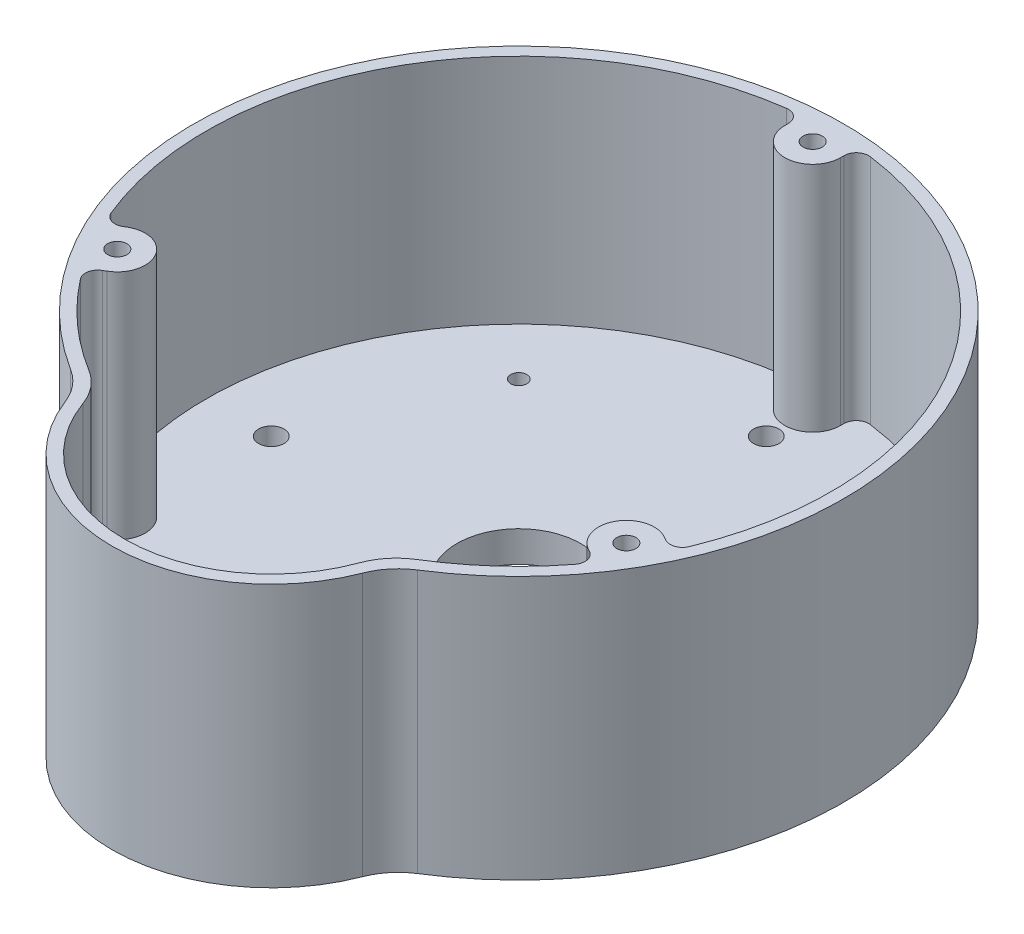
SolidWorks part; units mm, degrees
ref_plane "Plan de face" through (0, 0, 0) normal (0, 0, 1) x (1, 0, 0)
ref_plane "Plan de dessus" through (0, 0, 0) normal (0, 1, 0) x (1, 0, 0)
ref_plane "Plan de droite" through (0, 0, 0) normal (1, 0, 0) x (0, 0, -1)
sketch "Esquisse1" plane through (0, 0, 0) normal (0, 1, 0) x (1, 0, 0)
  line L0 (-51.4386, 28) -> (54.7147, 28) construction
  line L1 (-93.9383, 0) -> (92.9837, 0) construction
  line L2 (0, 84.3142) -> (0, -27.4159) construction
  line L3 (-79.8999, -42) -> (100.4836, -42) construction
  circle A0 centre (0, 0) radius 52.5
  circle A1 centre (0, 40) radius 2.05
  circle A2 centre (40, 0) radius 2.05
  circle A3 centre (0, -40) radius 2.05
  circle A4 centre (-40, 0) radius 2.05
  circle A5 centre (28, 28) radius 1.3
  circle A6 centre (20, -42) radius 1.3
  circle A7 centre (-20, -42) radius 1.3
  circle A8 centre (-28, 28) radius 1.3
  circle A9 centre (0, 0) radius 10
  point P14 (0, 0)
  dimension "D1" = 105
  dimension "D2" = 4.1
  dimension "D7" = 56
  dimension "D9" = 20
  dimension "D10" = 2.6
  dimension "D4" = 40
  dimension "D5" = 28
  dimension "D6" = 42
  dimension "D8" = 40
  dimension "D3" = 4
extrude "Boss.-Extru.2" add sketch "Esquisse1" along normal blind 5
sketch "Esquisse2" plane through (0, 5, 0) normal (0, 1, 0) x (1, 0, 0)
  line L0 (0, 90.2757) -> (0, -93.0238) construction
  line L1 (-4.5, 47.5) -> (-4.5, 50.2991) construction
  line L2 (4.5, 47.5) -> (4.5, 50.2991) construction
  line L3 (0, 0) -> (-88.0909, 50.8593) construction
  line L4 (0, 0) -> (91.089, 52.5902) construction
  line L5 (-4.5, 47.5) -> (-4.5, 48.0625)
  line L6 (4.5, 48.0625) -> (4.5, 47.5)
  line L7 (43.3862, -19.8529) -> (43.8733, -20.1341)
  line L8 (39.3733, -27.9283) -> (38.8862, -27.6471)
  line L9 (-38.8862, -27.6471) -> (-39.3733, -27.9283)
  line L10 (-43.8733, -20.1341) -> (-43.3862, -19.8529)
  circle A0 centre (0, 0) radius 50.5 construction
  circle A1 centre (0, 0) radius 52.5
  circle A2 centre (0, 0) radius 52.5
  circle A3 centre (0, 47.5) radius 4.5
  circle A4 centre (41.1362, -23.75) radius 4.5
  circle A5 centre (-41.1362, -23.75) radius 4.5
  arc A6 (-6.768, 50.0444) -> (-43.7343, 25.25) centre (0, 0) ccw
  arc A7 (6.768, 50.0444) -> (43.7343, 25.25) centre (0, 0) cw
  arc A8 (4.5, 48.0625) -> (6.768, 50.0444) centre (6.5, 48.0625) cw
  arc A9 (-6.768, 50.0444) -> (-4.5, 48.0625) centre (-6.5, 48.0625) cw
  arc A10 (46.7238, -19.1609) -> (43.7343, 25.25) centre (0, 0) ccw
  arc A11 (39.9557, -30.8835) -> (0, -50.5) centre (0, 0) cw
  arc A12 (39.3733, -27.9283) -> (39.9557, -30.8835) centre (38.3733, -29.6604) cw
  arc A13 (46.7238, -19.1609) -> (43.8733, -20.1341) centre (44.8733, -18.4021) cw
  arc A14 (-39.9557, -30.8835) -> (0, -50.5) centre (0, 0) ccw
  arc A15 (-46.7238, -19.1609) -> (-43.7343, 25.25) centre (0, 0) cw
  arc A16 (-43.8733, -20.1341) -> (-46.7238, -19.1609) centre (-44.8733, -18.4021) cw
  arc A17 (-39.9557, -30.8835) -> (-39.3733, -27.9283) centre (-38.3733, -29.6604) cw
  point P28 (0, 0)
  point P51 (0, 0)
  circle M7 centre (0, 0) radius 52.5
  dimension "D2" = 2
  dimension "D3" = 9
  dimension "D4" = 47.5
  dimension "D6" = 60
  dimension "D8" = 2
  dimension "D7" = 60
  dimension "D1" = 0
  dimension "D5" = 3
  dimension "D9" = 3
extrude "Boss.-Extru.3" add sketch "Esquisse2" along normal blind 37.5 contours A5 | A3 | A4 | A14 A17 L9 A5 L10 A16 A15 A6 A9 L5 A3 L6 A8 A7 A10 A13 L7 A4 L8 A12 A11 M7 region at (0, 5, -47.5) region at (-41.1362, 5, 23.75) region at (41.1362, 5, 23.75) region at (-51.0151, 5, 0)
sketch "Esquisse3" plane through (0, 42.5, 0) normal (0, 1, 0) x (1, 0, 0)
  circle A0 centre (0, 47.5) radius 3.35
  circle A3 centre (41.1362, -23.75) radius 3.35
  circle A4 centre (-41.1362, -23.75) radius 3.35
  circle A9 centre (0, 0) radius 52.5
  circle A10 centre (0, 0) radius 52.5
  point P13 (0, 0)
  dimension "D2" = 3
  dimension "D3" = 6.7
  dimension "D1" = 0
extrude "Enlèv. mat.-Extru.1" cut sketch "Esquisse3" against normal through all from offset 4 contours A0 | A4 | A3 offset against normal yes
sketch "Esquisse5" plane through (0, 42.5, 0) normal (0, 1, 0) x (1, 0, 0)
  arc A0 (-4.5, 47.5) -> (4.5, 47.5) centre (0, 47.5) ccw construction
  arc A1 (-4.5, 47.5) -> (4.5, 47.5) centre (0, 47.5) ccw
  circle A2 centre (0, 47.5) radius 1.55
  circle A3 centre (41.1362, -23.75) radius 1.55
  circle A4 centre (-41.1362, -23.75) radius 1.55
  point P11 (0, 0)
  dimension "D1" = 3.1
  dimension "D2" = 3
extrude "Enlèv. mat.-Extru.3" cut sketch "Esquisse5" against normal through all contours A4 | A3 | A2 region at (0, 42.5, -47.5) region at (41.1362, 42.5, 23.75) region at (-41.1362, 42.5, 23.75)
sketch "Esquisse6" plane through (0, 0, 0) normal (0, -1, 0) x (1, 0, 0)
  circle A0 centre (-20, 42) radius 3.75
  circle A1 centre (0, 0) radius 52.5
  circle A3 centre (20, 42) radius 3.75
  circle A4 centre (-28, -28) radius 3.75
  circle A5 centre (28, -28) radius 3.75
  circle A15 centre (0, 0) radius 52.5
  dimension "D2" = 7.5
  dimension "D1" = 0
extrude "Enlèv. mat.-Extru.4" cut sketch "Esquisse6" against normal blind 3 contours A0 | A3 | A5 | A4
sketch "Esquisse7" plane through (0, 0, 0) normal (0, 0, 1) x (1, 0, 0)
  line L0 (0, 56.3049) -> (0, -34.4214) construction
  line L1 (-52.5, 0) -> (52.5, 0) construction
  line L2 (-52.5, 0) -> (52.5, 0)
  line L3 (52.5, 42.5) -> (-52.5, 42.5) construction
  line L4 (52.5, 42.5) -> (-52.5, 42.5)
  line L5 (-25, 42.5) -> (-25, 5)
  line L6 (-25, 5) -> (25, 5)
  line L7 (25, 5) -> (25, 42.5)
  line L8 (-25, 42.5) -> (25, 42.5)
  dimension "D1" = 5
  dimension "D2" = 25
extrude "Enlèv. mat.-Extru.5" cut sketch "Esquisse7" along normal through all contours L0 L8 L5 L6 | L4 L0 L6 L7 region at (12.5, 23.75, 0) region at (-12.5, 23.75, 0)
sketch "Esquisse8" plane through (0, 0, 0) normal (0, 1, 0) x (1, 0, 0)
  line L0 (0, 4.2422) -> (0, -58.8142) construction
  line L6 (25, -46.1655) -> (25, -43.8777)
  line L7 (25, -46.1655) -> (25, -43.8777)
  line L8 (-38.8862, -27.6471) -> (-39.3733, -27.9283)
  line L9 (-38.8862, -27.6471) -> (-39.3733, -27.9283)
  line L10 (-25, -43.8777) -> (-25, -46.1655)
  line L11 (-25, -43.8777) -> (-25, -46.1655)
  line L12 (39.3733, -27.9283) -> (38.8862, -27.6471)
  line L13 (39.3733, -27.9283) -> (38.8862, -27.6471)
  line L25 (43.3862, -19.8529) -> (43.8733, -20.1341)
  line L26 (43.3862, -19.8529) -> (43.8733, -20.1341)
  line L27 (4.5, 48.0625) -> (4.5, 47.5)
  line L28 (4.5, 48.0625) -> (4.5, 47.5)
  line L29 (-4.5, 47.5) -> (-4.5, 48.0625)
  line L30 (-4.5, 47.5) -> (-4.5, 48.0625)
  line L31 (-43.8733, -20.1341) -> (-43.3862, -19.8529)
  line L32 (-43.8733, -20.1341) -> (-43.3862, -19.8529)
  arc A2 (-25, -46.1655) -> (25, -46.1655) centre (0, -40) ccw
  arc A4 (39.9557, -30.8835) -> (39.3733, -27.9283) centre (38.3733, -29.6604) ccw
  arc A11 (39.9557, -30.8835) -> (39.3733, -27.9283) centre (38.3733, -29.6604) ccw
  arc A12 (-39.3733, -27.9283) -> (-39.9557, -30.8835) centre (-38.3733, -29.6604) ccw
  arc A13 (-39.3733, -27.9283) -> (-39.9557, -30.8835) centre (-38.3733, -29.6604) ccw
  arc A14 (25, -43.8777) -> (39.9557, -30.8835) centre (0, 0) ccw
  arc A15 (25, -43.8777) -> (39.9557, -30.8835) centre (0, 0) ccw
  arc A16 (43.3862, -19.8529) -> (38.8862, -27.6471) centre (41.1362, -23.75) ccw
  arc A17 (43.3862, -19.8529) -> (38.8862, -27.6471) centre (41.1362, -23.75) ccw
  arc A18 (43.8733, -20.1341) -> (46.7238, -19.1609) centre (44.8733, -18.4021) ccw
  arc A19 (43.8733, -20.1341) -> (46.7238, -19.1609) centre (44.8733, -18.4021) ccw
  arc A20 (46.7238, -19.1609) -> (6.768, 50.0444) centre (0, 0) ccw
  arc A21 (46.7238, -19.1609) -> (6.768, 50.0444) centre (0, 0) ccw
  arc A22 (6.768, 50.0444) -> (4.5, 48.0625) centre (6.5, 48.0625) ccw
  arc A23 (6.768, 50.0444) -> (4.5, 48.0625) centre (6.5, 48.0625) ccw
  arc A24 (-4.5, 47.5) -> (4.5, 47.5) centre (0, 47.5) ccw
  arc A25 (-4.5, 47.5) -> (4.5, 47.5) centre (0, 47.5) ccw
  arc A48 (-4.5, 48.0625) -> (-6.768, 50.0444) centre (-6.5, 48.0625) ccw
  arc A49 (-4.5, 48.0625) -> (-6.768, 50.0444) centre (-6.5, 48.0625) ccw
  arc A50 (-6.768, 50.0444) -> (-46.7238, -19.1609) centre (0, 0) ccw
  arc A51 (-6.768, 50.0444) -> (-46.7238, -19.1609) centre (0, 0) ccw
  arc A52 (-46.7238, -19.1609) -> (-43.8733, -20.1341) centre (-44.8733, -18.4021) ccw
  arc A53 (-46.7238, -19.1609) -> (-43.8733, -20.1341) centre (-44.8733, -18.4021) ccw
  arc A54 (-38.8862, -27.6471) -> (-43.3862, -19.8529) centre (-41.1362, -23.75) ccw
  arc A55 (-38.8862, -27.6471) -> (-43.3862, -19.8529) centre (-41.1362, -23.75) ccw
  arc A56 (-39.9557, -30.8835) -> (-25, -43.8777) centre (0, 0) ccw
  arc A57 (-39.9557, -30.8835) -> (-25, -43.8777) centre (0, 0) ccw
  arc A58 (-25, -46.1655) -> (25, -46.1655) centre (0, 0) ccw
  arc A59 (-25, -46.1655) -> (25, -46.1655) centre (0, 0) ccw
  dimension "D2" = 40
  dimension "D1" = 0
extrude "Boss.-Extru.5" add sketch "Esquisse8" along normal blind 5 contours A59 | A59 region at (0, 0, 56.668)
sketch "Esquisse11" plane through (0, 5, 0) normal (0, 1, 0) x (1, 0, 0)
  line L0 (0, 0) -> (0, -73.5524) construction
  line L8 (25, -46.1655) -> (25, -43.8777)
  line L9 (39.3733, -27.9283) -> (38.8862, -27.6471)
  line L10 (43.3862, -19.8529) -> (43.8733, -20.1341)
  line L11 (4.5, 48.0625) -> (4.5, 47.5)
  line L12 (-4.5, 47.5) -> (-4.5, 48.0625)
  line L13 (-43.8733, -20.1341) -> (-43.3862, -19.8529)
  line L14 (-38.8862, -27.6471) -> (-39.3733, -27.9283)
  line L15 (-25, -43.8777) -> (-25, -46.1655)
  line L16 (25, -46.1655) -> (25, -43.8777)
  line L17 (39.3733, -27.9283) -> (38.8862, -27.6471)
  line L18 (43.3862, -19.8529) -> (43.8733, -20.1341)
  line L19 (4.5, 48.0625) -> (4.5, 47.5)
  line L20 (-4.5, 47.5) -> (-4.5, 48.0625)
  line L21 (-43.8733, -20.1341) -> (-43.3862, -19.8529)
  line L22 (-38.8862, -27.6471) -> (-39.3733, -27.9283)
  line L23 (-25, -43.8777) -> (-25, -46.1655)
  arc A0 (-25, -43.8777) -> (25, -43.8777) centre (0, 0) ccw
  arc A1 (-23.2531, -44.8279) -> (23.2531, -44.8279) centre (0, -40) ccw
  arc A14 (25, -43.8777) -> (39.9557, -30.8835) centre (0, 0) ccw
  arc A15 (39.9557, -30.8835) -> (39.3733, -27.9283) centre (38.3733, -29.6604) ccw
  arc A16 (43.3862, -19.8529) -> (38.8862, -27.6471) centre (41.1362, -23.75) ccw
  arc A17 (43.8733, -20.1341) -> (46.7238, -19.1609) centre (44.8733, -18.4021) ccw
  arc A18 (46.7238, -19.1609) -> (6.768, 50.0444) centre (0, 0) ccw
  arc A19 (6.768, 50.0444) -> (4.5, 48.0625) centre (6.5, 48.0625) ccw
  arc A20 (-4.5, 47.5) -> (4.5, 47.5) centre (0, 47.5) ccw
  arc A21 (-4.5, 48.0625) -> (-6.768, 50.0444) centre (-6.5, 48.0625) ccw
  arc A22 (-6.768, 50.0444) -> (-46.7238, -19.1609) centre (0, 0) ccw
  arc A23 (-46.7238, -19.1609) -> (-43.8733, -20.1341) centre (-44.8733, -18.4021) ccw
  arc A24 (-38.8862, -27.6471) -> (-43.3862, -19.8529) centre (-41.1362, -23.75) ccw
  arc A25 (-39.3733, -27.9283) -> (-39.9557, -30.8835) centre (-38.3733, -29.6604) ccw
  arc A26 (-39.9557, -30.8835) -> (-25, -43.8777) centre (0, 0) ccw
  arc A27 (-25, -46.1655) -> (25, -46.1655) centre (0, -40) ccw
  arc A28 (25, -43.8777) -> (39.9557, -30.8835) centre (0, 0) ccw
  arc A29 (39.9557, -30.8835) -> (39.3733, -27.9283) centre (38.3733, -29.6604) ccw
  arc A30 (43.3862, -19.8529) -> (38.8862, -27.6471) centre (41.1362, -23.75) ccw
  arc A31 (43.8733, -20.1341) -> (46.7238, -19.1609) centre (44.8733, -18.4021) ccw
  arc A32 (46.7238, -19.1609) -> (6.768, 50.0444) centre (0, 0) ccw
  arc A33 (6.768, 50.0444) -> (4.5, 48.0625) centre (6.5, 48.0625) ccw
  arc A34 (-4.5, 47.5) -> (4.5, 47.5) centre (0, 47.5) ccw
  arc A35 (-4.5, 48.0625) -> (-6.768, 50.0444) centre (-6.5, 48.0625) ccw
  arc A36 (-6.768, 50.0444) -> (-46.7238, -19.1609) centre (0, 0) ccw
  arc A37 (-46.7238, -19.1609) -> (-43.8733, -20.1341) centre (-44.8733, -18.4021) ccw
  arc A38 (-38.8862, -27.6471) -> (-43.3862, -19.8529) centre (-41.1362, -23.75) ccw
  arc A39 (-39.3733, -27.9283) -> (-39.9557, -30.8835) centre (-38.3733, -29.6604) ccw
  arc A40 (-39.9557, -30.8835) -> (-25, -43.8777) centre (0, 0) ccw
  arc A41 (-25, -46.1655) -> (25, -46.1655) centre (0, -40) ccw
  line M24 (25, -46.1655) -> (25, -43.8777)
  line M44 (-25, -43.8777) -> (-25, -46.1655)
  arc M45 (-25, -46.1655) -> (25, -46.1655) centre (0, -40) ccw
  dimension "D2" = 2
  dimension "D1" = 0
extrude "Boss.-Extru.9" add sketch "Esquisse11" along normal blind 37.5 contours L0 A1 A0 M44 M45 | A1 L0 A41 A0 M24 region at (15.199, 5, 58.6788) region at (-0.3322, 5, 64.749)
fillet "Congé1" radius 10 4 edges at (-23.2531, 23.75, 44.8279) (23.2531, 23.75, 44.8279) (25, 21.25, 46.1655) (-25, 21.25, 46.1655)
